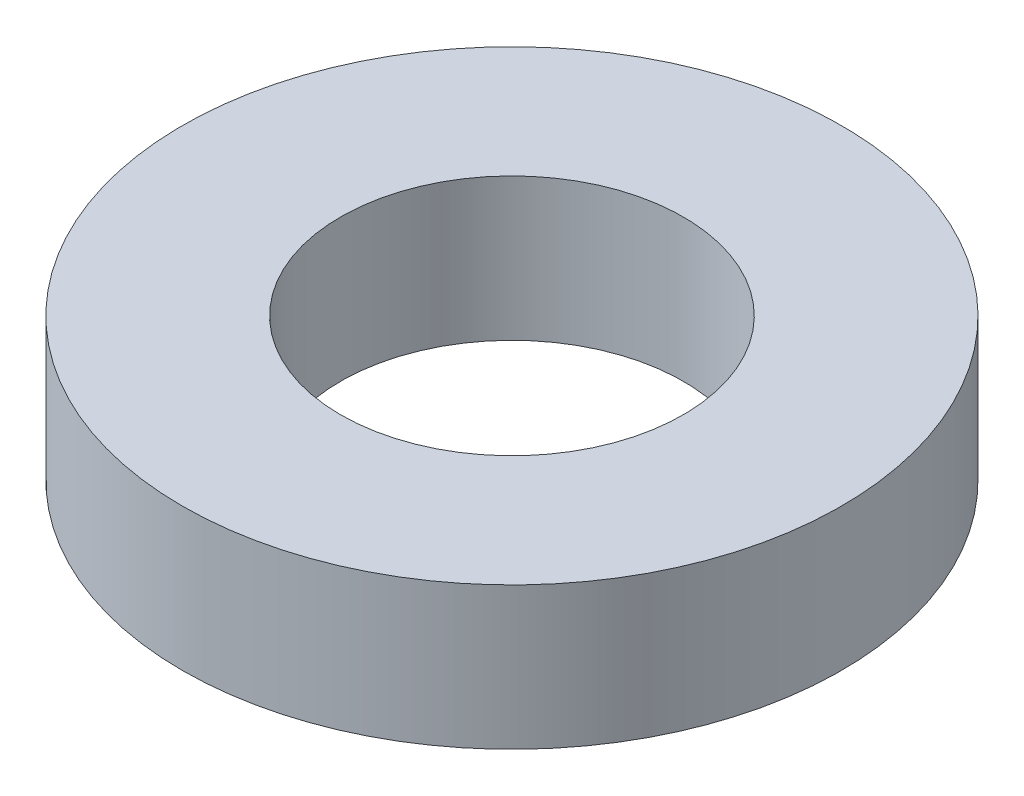
SolidWorks part; units mm, degrees
ref_plane "Front Plane" through (0, 0, 0) normal (0, 0, 1) x (1, 0, 0)
ref_plane "Top Plane" through (0, 0, 0) normal (0, 1, 0) x (1, 0, 0)
ref_plane "Right Plane" through (0, 0, 0) normal (1, 0, 0) x (0, 0, -1)
sketch "Sketch1" plane through (0, 0, 0) normal (0, 1, 0) x (1, 0, 0)
  circle A0 centre (0, 0) radius 62.5
  dimension "FLANGE_OD" = 125
extrude "Boss-Extrude1" add sketch "Sketch1" along normal blind 27
sketch "Sketch2" plane through (0, 0, 0) normal (0, 1, 0) x (1, 0, 0)
  circle A0 centre (0, 0) radius 32.5
  dimension "BORE_D" = 65
extrude "Cut-Extrude1" cut sketch "Sketch2" along normal through all
sketch "Sketch3" plane through (0, 27, 0) normal (0, 1, 0) x (1, 0, 0)
  circle A0 centre (0, 0) radius 17.8343 construction
  circle A1 centre (-17.8343, 0) radius 2.0528
  dimension "BOLT_D" = 4.1056
  dimension "BOLT_PCD" = 35.6685
extrude "Cut-Extrude2" cut sketch "Sketch3" against normal blind 17.0317 rebuild error yes
pattern_circular "CirPattern1" count 5 over 360 rebuild error yes
